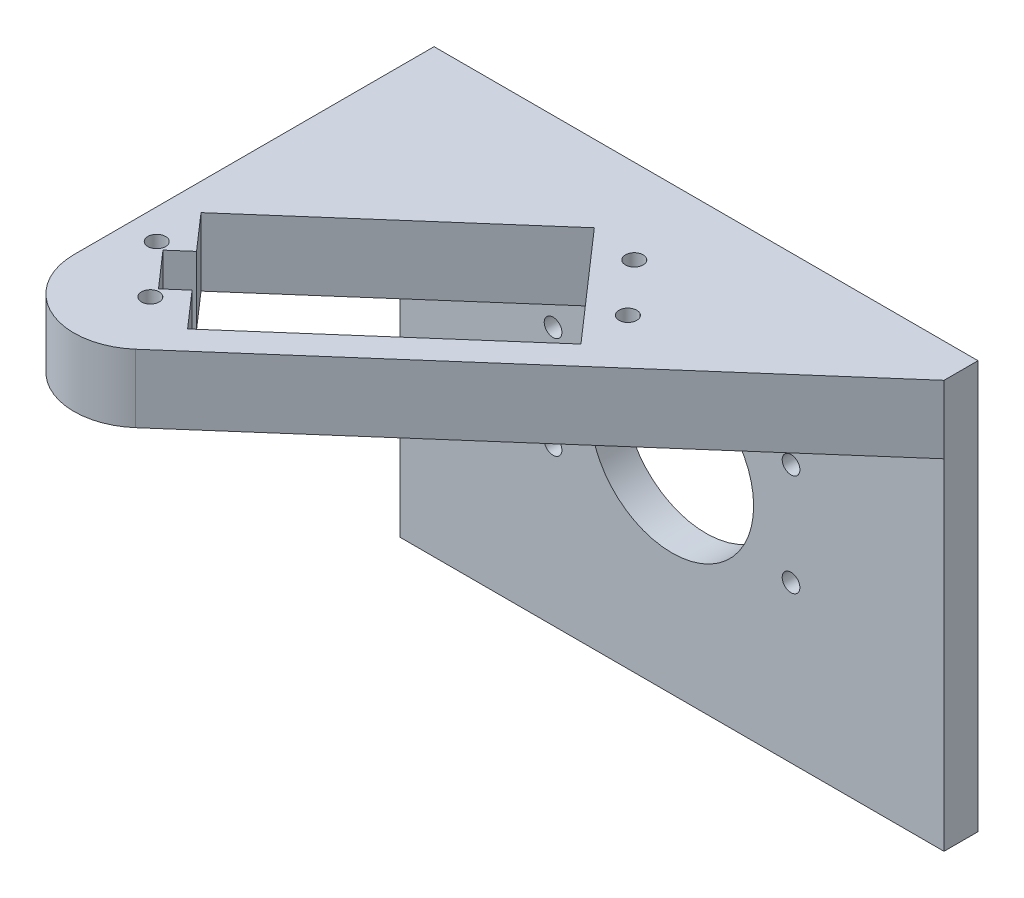
SolidWorks part; units mm, degrees
material "PLA"
ref_plane "Płaszczyzna przednia" through (0, 0, 0) normal (0, 0, 1) x (1, 0, 0)
ref_plane "Płaszczyzna górna" through (0, 0, 0) normal (0, 1, 0) x (1, 0, 0)
ref_plane "Płaszczyzna prawa" through (0, 0, 0) normal (1, 0, 0) x (0, 0, -1)
sketch "Szkic1" plane through (0, 0, 0) normal (0, 0, 1) x (1, 0, 0)
  line L1 (-40, 30) -> (40, 30)
  line L2 (-40, 30) -> (-40, -30)
  line L3 (-40, -30) -> (40, -30)
  line L4 (40, 30) -> (40, -30)
  line L5 (-40, 30) -> (40, -30) construction
  line L6 (-40, -30) -> (40, 30) construction
  point P0 (0, 0)
  dimension "D1" = 80
  dimension "D2" = 60
extrude "Dodanie-wyciągnięcie1" add sketch "Szkic1" along normal blind 5
ref_plane "Blat stołu" through (0, 30, 0) normal (0, 1, 0) x (1, 0, 0)
sketch "Szkic2" plane through (0, 30, 0) normal (0, 1, 0) x (1, 0, 0)
  line L0 (-40, -5) -> (-40, 0) construction
  line L1 (40, 0) -> (-40, 0)
  line L4 (-40, 0) -> (-40, -75)
  line L5 (40, 0) -> (40, -5)
  line L6 (40, -5) -> (-40, -75)
  dimension "D1" = 75
extrude "Dodanie-wyciągnięcie2" add sketch "Szkic2" against normal blind 10
sketch "Szkic5" plane through (0, 0, 5) normal (0, 0, 1) x (1, 0, 0)
  line L1 (40, -30) -> (40, 20) construction
  line L3 (-40, 20) -> (40, 20) construction
  point P0 (-17.5, 8)
  point P1 (17.5, 8)
  point P2 (17.5, -7)
  point P3 (-17.5, -7)
  dimension "D1" = 15
  dimension "D2" = 35
  dimension "D3" = 12
  dimension "D4" = 22.5
hole_wizard "Otwór pod śrubę M22" positions "Szkic 3D1" profile "Szkic6" hole size "M2" standard "ISO" end condition up to next
sketch3d "Szkic 3D1"
  point P0 (-17.5, 8, 5)
  point P3 (-17.5, -7, 5)
  point P6 (17.5, 8, 5)
  point P9 (17.5, -7, 5)
sketch "Szkic6" plane through (-17.5, 8, 5) normal (1, 0, 0) x (0, -1, 0)
  line L0 (0, 0) -> (0, 5)
  line L1 (0, 5) -> (1.3, 5)
  line L2 (1.3, 5) -> (1.3, 0)
  line L5 (1.3, 0) -> (0, 0)
  line L11 (0, -6.35) -> (0, 107.95) construction
  dimension "Średnica otworu na wylot" = 2.6
  dimension "Głębokość otworu na wylot" = 5
sketch "Szkic17" plane through (0, 20, 0) normal (0, -1, 0) x (1, 0, 0)
  line L1 (-36, 38.2808) -> (-5.1444, 11.2821)
  line L2 (-22.1714, 54.0849) -> (8.6842, 27.0862)
  line L4 (-40, 75) -> (40, 5) construction
  line L5 (-40, 5) -> (-40, 75) construction
  line L12 (-36, 38.2808) -> (-31.3905, 43.5488)
  line L13 (-5.1444, 11.2821) -> (8.6842, 27.0862)
  line L14 (-26.7809, 48.8169) -> (-29.415, 51.1216)
  line L16 (-29.415, 51.1216) -> (-34.0245, 45.8536)
  line L17 (-31.3905, 43.5488) -> (-34.0245, 45.8536)
  line L18 (-29.0857, 46.1828) -> (-34.0245, 45.8536) construction
  line L19 (-29.415, 51.1216) -> (-29.0857, 46.1828) construction
  line L22 (-26.7809, 48.8169) -> (-22.1714, 54.0849)
  point P9 (-29.0857, 46.1828)
  dimension "D1" = 21
  dimension "D2" = 41
  dimension "D3" = 4
  dimension "D4" = 4
  dimension "D5" = 7
extrude "Wytnij-wyciągnięcie2" cut sketch "Szkic17" against normal up to next
sketch "Szkic18" plane through (0, 20, 0) normal (0, -1, 0) x (1, 0, 0)
  line L0 (-35.5767, 45.2186) -> (-28.9916, 52.7444)
  line L1 (-35.5767, 45.2186) -> (1.8866, 12.4383)
  line L2 (-28.9916, 52.7444) -> (8.4716, 19.964)
  line L3 (1.8866, 12.4383) -> (8.4716, 19.964)
  line L4 (8.6842, 27.0862) -> (-22.1714, 54.0849) construction
  line L6 (-31.3905, 43.5488) -> (-36, 38.2808) construction
  dimension "D1" = 49.78
  dimension "D2" = 10
  dimension "D3" = 5.5
  dimension "D4" = 4.25
hole_wizard "Otwór pod śrubę M21" positions "Szkic19" profile "Szkic20" hole size "M2" standard "ISO" end condition up to next
sketch "Szkic19" plane through (0, 20, 0) normal (0, -1, 0) x (-1, 0, 0)
  point P0 (35.5767, -45.2186)
  point P3 (28.9916, -52.7444)
  point P6 (-8.4716, -19.964)
  point P9 (-1.8866, -12.4383)
sketch "Szkic20" plane through (-35.5767, 20, 45.2186) normal (1, 0, 0) x (0, 0, -1)
  line L0 (0, 0) -> (0, 10)
  line L1 (0, 10) -> (1.3, 10)
  line L2 (1.3, 10) -> (1.3, 0)
  line L5 (1.3, 0) -> (0, 0)
  line L11 (0, -6.35) -> (0, 107.95) construction
  dimension "Średnica otworu na wylot" = 2.6
  dimension "Głębokość otworu na wylot" = 10
fillet "Zaokrąglenie5" radius 10 1 edges at (-40, 25, 75)
hole_wizard "Otwór pod śrubę M201" positions "Szkic21" profile "Szkic22" hole size "M20" standard "ISO" end condition up to next
sketch "Szkic21" plane through (0, 0, 0) normal (0, 0, -1) x (-1, 0, 0)
  point P0 (0, 0)
sketch "Szkic22" plane through (0, 0, 0) normal (1, 0, 0) x (0, 1, 0)
  line L0 (0, 0) -> (0, 5)
  line L1 (0, 5) -> (12, 5)
  line L2 (12, 5) -> (12, 0)
  line L5 (12, 0) -> (0, 0)
  line L11 (0, -6.35) -> (0, 107.95) construction
  dimension "Średnica otworu na wylot" = 24
  dimension "Głębokość otworu na wylot" = 5
sketch "Szkic23" plane through (0, 20, 0) normal (0, -1, 0) x (1, 0, 0)
  line L0 (-21.3064, 39.376) -> (-28.9916, 52.7444) construction
  line L1 (-21.3064, 39.376) -> (-35.5767, 45.2186) construction
  line L2 (-21.3064, 39.376) -> (1.8866, 12.4383) construction
  line L3 (8.4716, 19.964) -> (-21.3064, 39.376) construction
  line L4 (-28.9916, 52.7444) -> (-32.8561, 50.5228)
  line L5 (-35.5767, 45.2186) -> (-38.4926, 38.0967)
  line L6 (1.8866, 12.4383) -> (7.1061, 16.9322)
  line L7 (8.4716, 19.964) -> (11.6759, 24.8794)
  point P0 (-21.3064, 39.376)
  dimension "D1" = 15.42
  dimension "D2" = 15.42
ref_axis "Oś1" through (-21.3064, 20, 39.376) along (0, 1, 0)
